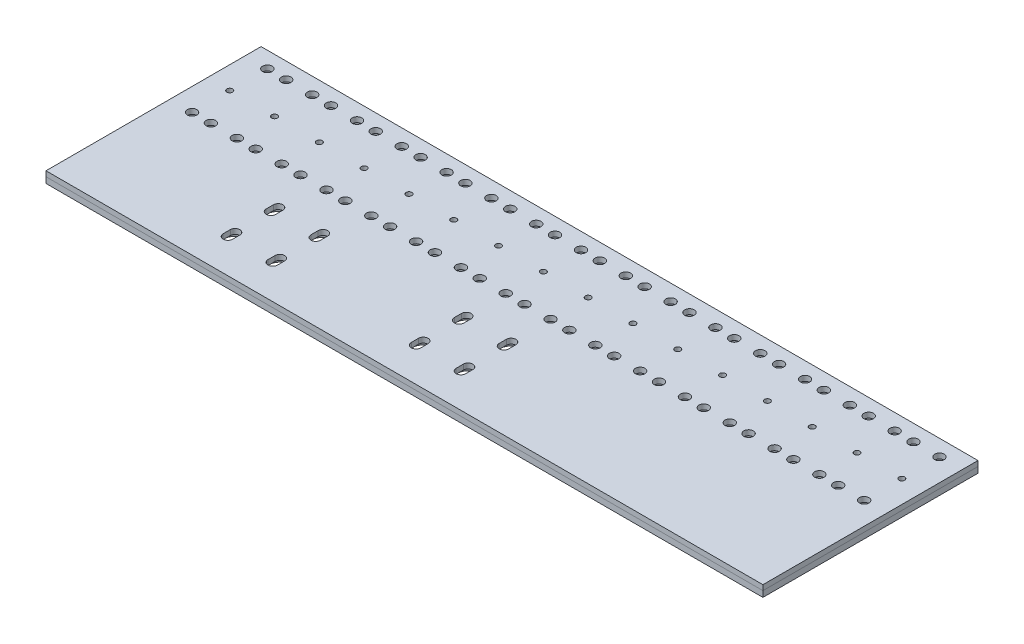
SolidWorks part; units mm, degrees
ref_plane "Front Plane" through (0, 0, 0) normal (0, 0, 1) x (1, 0, 0)
ref_plane "Top Plane" through (0, 0, 0) normal (0, 1, 0) x (1, 0, 0)
ref_plane "Right Plane" through (0, 0, 0) normal (1, 0, 0) x (0, 0, -1)
sketch "Sketch1" plane through (0, 0, 0) normal (0, 1, 0) x (1, 0, 0)
  line L0 (-187.5, 30) -> (-162.5, 30) construction
  line L1 (-200, 60) -> (200, 60)
  line L2 (-200, 60) -> (-200, -60)
  line L3 (-200, -60) -> (200, -60)
  line L4 (200, 60) -> (200, -60)
  line L5 (-200, -27) -> (200, -27) construction
  line L6 (12.5, 60) -> (12.5, -60) construction
  line L7 (-187.5, 51) -> (-162.5, 51) construction
  line L8 (-95.15, -13) -> (-95.15, -17)
  line L9 (9.85, -13) -> (15.15, -13)
  line L10 (9.85, -13) -> (9.85, -17)
  line L11 (9.85, -17) -> (15.15, -17)
  line L12 (15.15, -13) -> (15.15, -17)
  line L13 (-95.15, -13) -> (-89.85, -13)
  line L14 (-89.85, -13) -> (-89.85, -17)
  line L15 (-95.15, -17) -> (-89.85, -17)
  line L16 (9.85, -13) -> (-95.15, -13) construction
  line L17 (9.85, -37) -> (15.15, -37)
  line L18 (15.15, -41) -> (15.15, -37)
  line L19 (9.85, -41) -> (15.15, -41)
  line L20 (9.85, -41) -> (9.85, -37)
  line L21 (-95.15, -41) -> (-89.85, -41)
  line L22 (-89.85, -41) -> (-89.85, -37)
  line L23 (-95.15, -37) -> (-89.85, -37)
  line L24 (-95.15, -41) -> (-95.15, -37)
  line L25 (-177, 51) -> (-152, 51) construction
  line L26 (-120.15, -13) -> (-120.15, -17)
  line L27 (-15.15, -13) -> (-9.85, -13)
  line L28 (-15.15, -13) -> (-15.15, -17)
  line L29 (-15.15, -17) -> (-9.85, -17)
  line L30 (-9.85, -13) -> (-9.85, -17)
  line L31 (-120.15, -13) -> (-114.85, -13)
  line L32 (-114.85, -13) -> (-114.85, -17)
  line L33 (-120.15, -17) -> (-114.85, -17)
  line L34 (-15.15, -37) -> (-9.85, -37)
  line L35 (-9.85, -41) -> (-9.85, -37)
  line L36 (-15.15, -41) -> (-9.85, -41)
  line L37 (-15.15, -41) -> (-15.15, -37)
  line L38 (-120.15, -41) -> (-114.85, -41)
  line L39 (-114.85, -41) -> (-114.85, -37)
  line L40 (-120.15, -37) -> (-114.85, -37)
  line L41 (-120.15, -41) -> (-120.15, -37)
  line L42 (-95.15, -13) -> (-120.15, -13) construction
  circle A0 centre (-187.5, 30) radius 1.6
  circle A1 centre (-162.5, 30) radius 1.6
  circle A2 centre (-137.5, 30) radius 1.6
  circle A3 centre (-112.5, 30) radius 1.6
  circle A4 centre (-87.5, 30) radius 1.6
  circle A5 centre (-62.5, 30) radius 1.6
  circle A6 centre (-37.5, 30) radius 1.6
  circle A7 centre (-12.5, 30) radius 1.6
  circle A8 centre (12.5, 30) radius 1.6
  circle A9 centre (37.5, 30) radius 1.6
  circle A10 centre (62.5, 30) radius 1.6
  circle A11 centre (87.5, 30) radius 1.6
  circle A12 centre (112.5, 30) radius 1.6
  circle A13 centre (137.5, 30) radius 1.6
  circle A14 centre (162.5, 30) radius 1.6
  circle A15 centre (187.5, 30) radius 1.6
  circle A16 centre (12.5, -13) radius 2.65
  circle A17 centre (-92.5, -13) radius 2.65
  circle A18 centre (12.5, -41) radius 2.65
  circle A19 centre (-92.5, -41) radius 2.65
  circle A20 centre (-187.5, 9) radius 2.65
  circle A21 centre (-187.5, 51) radius 2.65
  circle A22 centre (-162.5, 51) radius 2.65
  circle A23 centre (-162.5, 9) radius 2.65
  circle A24 centre (-137.5, 51) radius 2.65
  circle A25 centre (-137.5, 9) radius 2.65
  circle A26 centre (-112.5, 51) radius 2.65
  circle A27 centre (-112.5, 9) radius 2.65
  circle A28 centre (-87.5, 51) radius 2.65
  circle A29 centre (-87.5, 9) radius 2.65
  circle A30 centre (-62.5, 51) radius 2.65
  circle A31 centre (-62.5, 9) radius 2.65
  circle A32 centre (-37.5, 51) radius 2.65
  circle A33 centre (-37.5, 9) radius 2.65
  circle A34 centre (-12.5, 51) radius 2.65
  circle A35 centre (-12.5, 9) radius 2.65
  circle A36 centre (12.5, 51) radius 2.65
  circle A37 centre (12.5, 9) radius 2.65
  circle A38 centre (37.5, 51) radius 2.65
  circle A39 centre (37.5, 9) radius 2.65
  circle A40 centre (62.5, 51) radius 2.65
  circle A41 centre (62.5, 9) radius 2.65
  circle A42 centre (87.5, 51) radius 2.65
  circle A43 centre (87.5, 9) radius 2.65
  circle A44 centre (112.5, 51) radius 2.65
  circle A45 centre (112.5, 9) radius 2.65
  circle A46 centre (137.5, 51) radius 2.65
  circle A47 centre (137.5, 9) radius 2.65
  circle A48 centre (162.5, 51) radius 2.65
  circle A49 centre (162.5, 9) radius 2.65
  circle A50 centre (187.5, 51) radius 2.65
  circle A51 centre (187.5, 9) radius 2.65
  circle A52 centre (12.5, -17) radius 2.65
  circle A53 centre (-92.5, -17) radius 2.65
  circle A54 centre (12.5, -37) radius 2.65
  circle A55 centre (-92.5, -37) radius 2.65
  circle A56 centre (-177, 51) radius 2.65
  circle A57 centre (-177, 9) radius 2.65
  circle A58 centre (-152, 51) radius 2.65
  circle A59 centre (-152, 9) radius 2.65
  circle A60 centre (-127, 51) radius 2.65
  circle A61 centre (-127, 9) radius 2.65
  circle A62 centre (-102, 51) radius 2.65
  circle A63 centre (-102, 9) radius 2.65
  circle A64 centre (-77, 51) radius 2.65
  circle A65 centre (-77, 9) radius 2.65
  circle A66 centre (-52, 51) radius 2.65
  circle A67 centre (-52, 9) radius 2.65
  circle A68 centre (-27, 51) radius 2.65
  circle A69 centre (-27, 9) radius 2.65
  circle A70 centre (-2, 51) radius 2.65
  circle A71 centre (-2, 9) radius 2.65
  circle A72 centre (23, 51) radius 2.65
  circle A73 centre (23, 9) radius 2.65
  circle A74 centre (48, 51) radius 2.65
  circle A75 centre (48, 9) radius 2.65
  circle A76 centre (73, 51) radius 2.65
  circle A77 centre (73, 9) radius 2.65
  circle A78 centre (98, 51) radius 2.65
  circle A79 centre (98, 9) radius 2.65
  circle A80 centre (123, 51) radius 2.65
  circle A81 centre (123, 9) radius 2.65
  circle A82 centre (148, 51) radius 2.65
  circle A83 centre (148, 9) radius 2.65
  circle A84 centre (173, 51) radius 2.65
  circle A85 centre (173, 9) radius 2.65
  circle A86 centre (-12.5, -13) radius 2.65
  circle A87 centre (-117.5, -13) radius 2.65
  circle A88 centre (-12.5, -41) radius 2.65
  circle A89 centre (-117.5, -41) radius 2.65
  circle A90 centre (-12.5, -17) radius 2.65
  circle A91 centre (-117.5, -17) radius 2.65
  circle A92 centre (-12.5, -37) radius 2.65
  circle A93 centre (-117.5, -37) radius 2.65
  point P4 (0, 60)
  point P5 (200, 0)
  dimension "D3" = 12.5
  dimension "D5" = 3.2
  dimension "D6" = 16
  dimension "D9" = 5.3
  dimension "D12" = 5.3
  dimension "D16" = 4
  dimension "D19" = 10.5
  dimension "D1" = 120
  dimension "D2" = 400
  dimension "D4" = 30
  dimension "D7" = 25
  dimension "D8" = 57
  dimension "D10" = 14
  dimension "D11" = 105
  dimension "D13" = 21
  dimension "D15" = 25
  dimension "D17" = 2
  dimension "D18" = 105
  dimension "D21" = 25
  dimension "D23" = 25
  dimension "D14" = 16
  dimension "D20" = 15
  dimension "D22" = 2
extrude "Boss-Extrude1" add sketch "Sketch1" along normal blind 2.89 contours L4 L1 L2 L3 A53 L8 A17 L14 A52 L10 A16 L12 A51 A48 A47 A44 A43 A40 A39 A36 A35 A32 A31 A28 A27 A24 A23 A21 A20 A15
sketch "Sketch2" plane through (0, 0, 0) normal (0, -1, 0) x (1, 0, 0)
  line L0 (-200, -60) -> (200, -60) construction
  line L1 (200, -60) -> (200, 60) construction
  line L2 (-200, 60) -> (200, 60) construction
  line L3 (-200, -60) -> (-200, 60) construction
  line L4 (-200, -60) -> (200, -60)
  line L5 (200, -60) -> (200, 60)
  line L6 (-200, 60) -> (200, 60)
  line L7 (-200, -60) -> (-200, 60)
  line L8 (-187.5, -9) -> (-162.5, -9) construction
  line L9 (-92.5, 43.65) -> (-92.5, 10.35) construction
  line L10 (12.5, 43.65) -> (12.5, 10.35) construction
  line L11 (12.5, 27) -> (-92.5, 27) construction
  line L12 (-95.15, 41) -> (-89.85, 41) construction
  line L13 (-95.15, 37) -> (-89.85, 37) construction
  line L14 (-98.5, 17) -> (-86.5, 17)
  line L15 (-98.5, 41) -> (-86.5, 41)
  line L16 (-98.5, 41) -> (-98.5, 37)
  line L17 (-98.5, 37) -> (-86.5, 37)
  line L18 (-86.5, 41) -> (-86.5, 37)
  line L19 (-86.5, 13) -> (-86.5, 17)
  line L20 (-98.5, 13) -> (-86.5, 13)
  line L21 (-98.5, 13) -> (-98.5, 17)
  line L22 (6.5, 41) -> (6.5, 37)
  line L23 (6.5, 41) -> (18.5, 41)
  line L24 (18.5, 41) -> (18.5, 37)
  line L25 (6.5, 37) -> (18.5, 37)
  line L26 (6.5, 17) -> (18.5, 17)
  line L27 (18.5, 13) -> (18.5, 17)
  line L28 (6.5, 13) -> (18.5, 13)
  line L29 (6.5, 13) -> (6.5, 17)
  line L30 (-92.5, 41) -> (12.5, 41) construction
  line L31 (-187.5, -30) -> (-162.5, -30) construction
  line L32 (-177, -9) -> (-152, -9) construction
  line L33 (-123.5, 17) -> (-111.5, 17)
  line L34 (-123.5, 41) -> (-111.5, 41)
  line L35 (-123.5, 41) -> (-123.5, 37)
  line L36 (-123.5, 37) -> (-111.5, 37)
  line L37 (-111.5, 41) -> (-111.5, 37)
  line L38 (-111.5, 13) -> (-111.5, 17)
  line L39 (-123.5, 13) -> (-111.5, 13)
  line L40 (-123.5, 13) -> (-123.5, 17)
  line L41 (-18.5, 41) -> (-18.5, 37)
  line L42 (-18.5, 41) -> (-6.5, 41)
  line L43 (-6.5, 41) -> (-6.5, 37)
  line L44 (-18.5, 37) -> (-6.5, 37)
  line L45 (-18.5, 17) -> (-6.5, 17)
  line L46 (-6.5, 13) -> (-6.5, 17)
  line L47 (-18.5, 13) -> (-6.5, 13)
  line L48 (-18.5, 13) -> (-18.5, 17)
  line L49 (-117.5, 43.65) -> (-117.5, 10.35) construction
  line L50 (-12.5, 43.65) -> (-12.5, 10.35) construction
  line L51 (-120.15, 41) -> (-114.85, 41) construction
  line L52 (-120.15, 37) -> (-114.85, 37) construction
  line L57 (-98.5, 17) -> (-123.5, 17) construction
  line L58 (-225, -60) -> (175, -60) [skipped]
  line L59 (175, -60) -> (175, 60) [skipped]
  line L60 (-225, 60) -> (175, 60) [skipped]
  line L61 (-225, -60) -> (-225, 60) [skipped]
  circle A0 centre (-187.5, -30) radius 4
  circle A1 centre (-187.5, -9) radius 6
  circle A2 centre (-187.5, -51) radius 6
  circle A3 centre (-162.5, -9) radius 6
  circle A4 centre (-162.5, -30) radius 4
  circle A5 centre (-162.5, -51) radius 6
  circle A6 centre (-137.5, -9) radius 6
  circle A7 centre (-137.5, -30) radius 4
  circle A8 centre (-137.5, -51) radius 6
  circle A9 centre (-112.5, -9) radius 6
  circle A10 centre (-112.5, -30) radius 4
  circle A11 centre (-112.5, -51) radius 6
  circle A12 centre (-87.5, -9) radius 6
  circle A13 centre (-87.5, -30) radius 4
  circle A14 centre (-87.5, -51) radius 6
  circle A15 centre (-62.5, -9) radius 6
  circle A16 centre (-62.5, -30) radius 4
  circle A17 centre (-62.5, -51) radius 6
  circle A18 centre (-37.5, -9) radius 6
  circle A19 centre (-37.5, -30) radius 4
  circle A20 centre (-37.5, -51) radius 6
  circle A21 centre (-12.5, -9) radius 6
  circle A22 centre (-12.5, -30) radius 4
  circle A23 centre (-12.5, -51) radius 6
  circle A24 centre (12.5, -9) radius 6
  circle A25 centre (12.5, -30) radius 4
  circle A26 centre (12.5, -51) radius 6
  circle A27 centre (37.5, -9) radius 6
  circle A28 centre (37.5, -30) radius 4
  circle A29 centre (37.5, -51) radius 6
  circle A30 centre (62.5, -9) radius 6
  circle A31 centre (62.5, -30) radius 4
  circle A32 centre (62.5, -51) radius 6
  circle A33 centre (87.5, -9) radius 6
  circle A34 centre (87.5, -30) radius 4
  circle A35 centre (87.5, -51) radius 6
  circle A36 centre (112.5, -9) radius 6
  circle A37 centre (112.5, -30) radius 4
  circle A38 centre (112.5, -51) radius 6
  circle A39 centre (137.5, -9) radius 6
  circle A40 centre (137.5, -30) radius 4
  circle A41 centre (137.5, -51) radius 6
  circle A42 centre (162.5, -9) radius 6
  circle A43 centre (162.5, -30) radius 4
  circle A44 centre (162.5, -51) radius 6
  circle A45 centre (187.5, -9) radius 6
  circle A46 centre (187.5, -30) radius 4
  circle A47 centre (187.5, -51) radius 6
  arc A48 (-89.85, 41) -> (-95.15, 41) centre (-92.5, 41) ccw construction
  arc A49 (-95.15, 13) -> (-89.85, 13) centre (-92.5, 13) ccw construction
  arc A50 (15.15, 41) -> (9.85, 41) centre (12.5, 41) ccw construction
  arc A51 (9.85, 13) -> (15.15, 13) centre (12.5, 13) ccw construction
  circle A52 centre (-92.5, 41) radius 6
  circle A53 centre (-92.5, 37) radius 6
  circle A54 centre (-92.5, 17) radius 6
  circle A55 centre (-92.5, 13) radius 6
  circle A56 centre (12.5, 41) radius 6
  circle A57 centre (12.5, 37) radius 6
  circle A58 centre (12.5, 17) radius 6
  circle A59 centre (12.5, 13) radius 6
  circle A60 centre (-177, -51) radius 6
  circle A61 centre (-177, -9) radius 6
  circle A62 centre (-152, -9) radius 6
  circle A63 centre (-152, -51) radius 6
  circle A64 centre (-127, -9) radius 6
  circle A65 centre (-127, -51) radius 6
  circle A66 centre (-102, -9) radius 6
  circle A67 centre (-102, -51) radius 6
  circle A68 centre (-77, -9) radius 6
  circle A69 centre (-77, -51) radius 6
  circle A70 centre (-52, -9) radius 6
  circle A71 centre (-52, -51) radius 6
  circle A72 centre (-27, -9) radius 6
  circle A73 centre (-27, -51) radius 6
  circle A74 centre (-2, -9) radius 6
  circle A75 centre (-2, -51) radius 6
  circle A76 centre (23, -9) radius 6
  circle A77 centre (23, -51) radius 6
  circle A78 centre (48, -9) radius 6
  circle A79 centre (48, -51) radius 6
  circle A80 centre (73, -9) radius 6
  circle A81 centre (73, -51) radius 6
  circle A82 centre (98, -9) radius 6
  circle A83 centre (98, -51) radius 6
  circle A84 centre (123, -9) radius 6
  circle A85 centre (123, -51) radius 6
  circle A86 centre (148, -9) radius 6
  circle A87 centre (148, -51) radius 6
  circle A88 centre (173, -9) radius 6
  circle A89 centre (173, -51) radius 6
  circle A90 centre (-117.5, 41) radius 6
  circle A91 centre (-117.5, 37) radius 6
  circle A92 centre (-117.5, 17) radius 6
  circle A93 centre (-117.5, 13) radius 6
  circle A94 centre (-12.5, 41) radius 6
  circle A95 centre (-12.5, 37) radius 6
  circle A96 centre (-12.5, 17) radius 6
  circle A97 centre (-12.5, 13) radius 6
  dimension "D1" = 8
  dimension "D2" = 12
  dimension "D3" = 12
  dimension "D6" = 12
  dimension "D7" = 2
  dimension "D9" = 15
  dimension "D5" = 25
  dimension "D8" = 105
  dimension "D10" = 25
  dimension "D12" = 25
  dimension "D4" = 16
  dimension "D11" = 2
extrude "Boss-Extrude2" add sketch "Sketch2" along normal blind 3.27 separate body contours L7 L4 L5 L6 A95 L41 A94 L43 A91 L35 A90 L37 A89 A44 A87 A41 A85 A38 A83 A35 A81 A32 A79 A29 A77 A26 A75 A23 A73 A20 A71 A17 A69 A14 A67 A11
